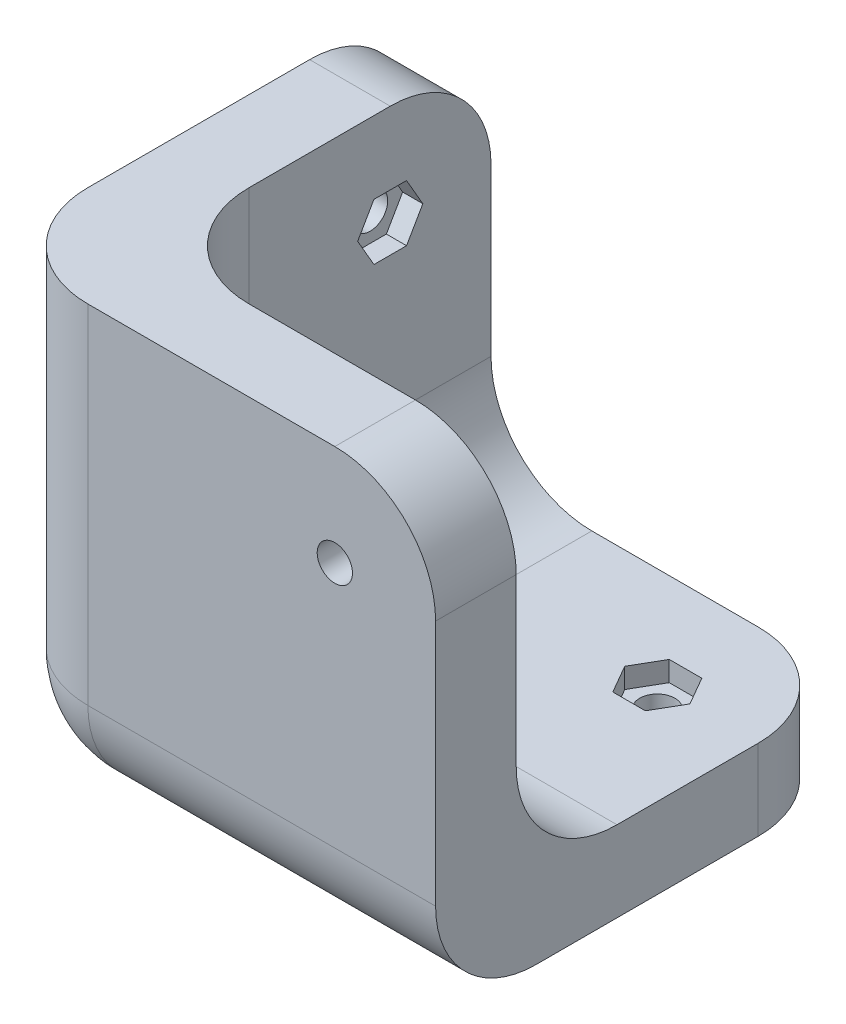
SolidWorks part; units mm, degrees
ref_plane "Front Plane" through (0, 0, 0) normal (0, 0, 1) x (1, 0, 0)
ref_plane "Top Plane" through (0, 0, 0) normal (0, 1, 0) x (1, 0, 0)
ref_plane "Right Plane" through (0, 0, 0) normal (1, 0, 0) x (0, 0, -1)
sketch "Sketch1" plane through (0, 0, 0) normal (0, 0, 1) x (1, 0, 0)
  line L1 (0, 0) -> (34.5, 0)
  line L2 (0, 0) -> (0, 4)
  line L3 (0, 4) -> (34.5, 4)
  line L4 (34.5, 0) -> (34.5, 4)
  line L5 (0, 4) -> (4, 4)
  line L6 (0, 4) -> (0, 34.5)
  line L7 (0, 34.5) -> (4, 34.5)
  line L8 (4, 4) -> (4, 34.5)
  line L9 (4, 34.5) -> (8, 34.5)
  line L10 (4, 34.5) -> (4, 4)
  line L11 (4, 4) -> (8, 4)
  line L12 (8, 34.5) -> (8, 4)
  line L13 (8, 4) -> (34.5, 4)
  line L14 (8, 4) -> (8, 8)
  line L15 (8, 8) -> (34.5, 8)
  line L16 (34.5, 4) -> (34.5, 8)
  line L17 (0, 34.5) -> (4, 34.5)
  line L18 (0, 34.5) -> (0, 44.5)
  line L19 (0, 44.5) -> (4, 44.5)
  line L20 (4, 34.5) -> (4, 44.5)
  line L21 (4, 44.5) -> (8, 44.5)
  line L22 (4, 44.5) -> (4, 34.5)
  line L23 (4, 34.5) -> (8, 34.5)
  line L24 (8, 44.5) -> (8, 34.5)
  line L25 (34.5, 8) -> (44.5, 8)
  line L26 (34.5, 8) -> (34.5, 4)
  line L27 (34.5, 4) -> (44.5, 4)
  line L28 (44.5, 8) -> (44.5, 4)
  line L29 (44.5, 4) -> (34.5, 4)
  line L30 (44.5, 4) -> (44.5, 0)
  line L31 (44.5, 0) -> (34.5, 0)
  line L32 (34.5, 4) -> (34.5, 0)
  line L33 (8, 44.5) -> (44.5, 44.5)
  line L34 (8, 44.5) -> (8, 8)
  line L35 (8, 8) -> (44.5, 8)
  line L36 (44.5, 44.5) -> (44.5, 8)
  dimension "D1" = 34.5
  dimension "D2" = 34.5
  dimension "D3" = 4
  dimension "D4" = 10
extrude "Boss-Extrude1" add sketch "Sketch1" along normal blind 42 contours L36 L33 L24 L12 L15 L25 | L24 L21 L20 L9 | L7 L20 L19 L18 | L3 L8 L7 L6 | L12 L9 L8 L3 | L1 L4 L3 L2 | L3 L16 L15 L12 | L28 L25 L16 L27 | L31 L30 L27 L4 region at (17.25, 2, 0) region at (39.5, 2, 0) region at (2, 19.25, 0) region at (21.25, 6, 0) region at (39.5, 6, 0) region at (6, 19.25, 0) region at (2, 39.5, 0) region at (26.25, 26.25, 0) region at (6, 39.5, 0)
extrude "Cut-Extrude1" cut sketch "Sketch1<3>" along normal offset from surface (34 mm away) 8 contours L36 L33 L24 L12 L15 L25 region at (26.25, 26.25, 0) up to face at (22.25, 22.25, 42)
sketch "Sketch1<3>" plane through (0, 0, 0) normal (0, 0, 1) x (1, 0, 0) same geometry as "Sketch1"
sketch "Sketch3" plane through (0, 0, 34) normal (0, 0, -1) x (-1, 0, 0)
  line L2 (-8, 44.5) -> (-44.5, 44.5) construction
  line L3 (-31.2668, 34.5) -> (-32.8834, 37.3)
  line L4 (-32.8834, 37.3) -> (-36.1166, 37.3)
  line L5 (-36.1166, 37.3) -> (-37.7332, 34.5)
  line L6 (-37.7332, 34.5) -> (-36.1166, 31.7)
  line L7 (-36.1166, 31.7) -> (-32.8834, 31.7)
  line L8 (-32.8834, 31.7) -> (-31.2668, 34.5)
  line L9 (-44.5, 44.5) -> (-44.5, 8) construction
  circle A0 centre (-34.5, 34.5) radius 1.75
  circle A1 centre (-34.5, 34.5) radius 2.8 construction
  point P4 (0, 0)
  point P6 (-38.6365, 37.4885)
  dimension "D1" = 3.5
  dimension "D4" = 5.6
  dimension "D2" = 10
  dimension "D3" = 10
sketch "Sketch4" plane through (8, 0, 0) normal (1, 0, 0) x (0, 0, -1)
  line L3 (-6.7668, 34.5) -> (-8.3834, 37.3)
  line L4 (-8.3834, 37.3) -> (-11.6166, 37.3)
  line L5 (-11.6166, 37.3) -> (-13.2332, 34.5)
  line L6 (-13.2332, 34.5) -> (-11.6166, 31.7)
  line L7 (-11.6166, 31.7) -> (-8.3834, 31.7)
  line L8 (-8.3834, 31.7) -> (-6.7668, 34.5)
  line L10 (-34, 44.5) -> (0, 44.5) construction
  line L11 (0, 44.5) -> (0, 8) construction
  circle A0 centre (-10, 34.5) radius 1.75
  circle A1 centre (-10, 34.5) radius 2.8 construction
  dimension "D1" = 3.5
  dimension "D4" = 5.6
  dimension "D2" = 10
  dimension "D3" = 10
sketch "Sketch5" plane through (0, 8, 0) normal (0, 1, 0) x (1, 0, 0)
  line L3 (37.7332, -10) -> (36.1166, -7.2)
  line L4 (36.1166, -7.2) -> (32.8834, -7.2)
  line L5 (32.8834, -7.2) -> (31.2668, -10)
  line L6 (31.2668, -10) -> (32.8834, -12.8)
  line L7 (32.8834, -12.8) -> (36.1166, -12.8)
  line L8 (36.1166, -12.8) -> (37.7332, -10)
  line L10 (44.5, -34) -> (44.5, 0) construction
  line L11 (8, 0) -> (44.5, 0) construction
  circle A0 centre (34.5, -10) radius 1.75
  circle A1 centre (34.5, -10) radius 2.8 construction
  dimension "D1" = 3.5
  dimension "D4" = 5.6
  dimension "D2" = 10
  dimension "D3" = 10
extrude "Cut-Extrude2" cut sketch "Sketch3" against normal through all contours A0 region at (34.5, 34.5, 34)
extrude "Cut-Extrude3" cut sketch "Sketch3<3>" against normal offset from surface (2 mm away) 2 up to face at (32.75, 34.5, 34)
sketch "Sketch3<3>" plane through (0, 0, 34) normal (0, 0, -1) x (-1, 0, 0) same geometry as "Sketch3"
extrude "Cut-Extrude4" cut sketch "Sketch4" against normal through all contours A0 region at (8, 34.5, 10)
extrude "Cut-Extrude5" cut sketch "Sketch4<3>" against normal offset from surface (2 mm away) 2 up to face at (8, 36.25, 10)
sketch "Sketch4<3>" plane through (8, 0, 0) normal (1, 0, 0) x (0, 0, -1) same geometry as "Sketch4"
extrude "Cut-Extrude6" cut sketch "Sketch5" against normal through all contours A0 region at (34.5, 8, 10)
extrude "Cut-Extrude7" cut sketch "Sketch5<3>" against normal offset from surface (2 mm away) 2 up to face at (34.5, 8, 11.75)
sketch "Sketch5<3>" plane through (0, 8, 0) normal (0, 1, 0) x (1, 0, 0) same geometry as "Sketch5"
fillet "Fillet1" radius 10 9 edges at (0, 0, 21) (22.25, 0, 42) (0, 22.25, 42) (8, 26.25, 34) (8, 8, 17) (26.25, 8, 34) (4, 44.5, 0) (44.5, 4, 0) (44.5, 44.5, 38)
